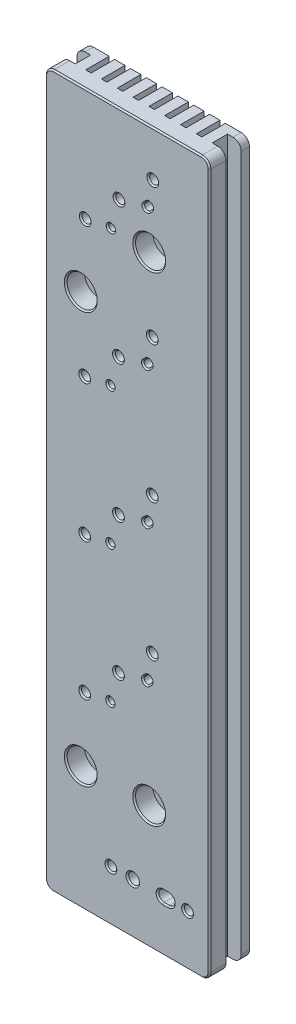
SolidWorks part; units mm, degrees
material "AISI 304"
ref_plane "前视基准面" through (0, 0, 0) normal (0, 0, 1) x (1, 0, 0)
ref_plane "上视基准面" through (0, 0, 0) normal (0, 1, 0) x (1, 0, 0)
ref_plane "右视基准面" through (0, 0, 0) normal (1, 0, 0) x (0, 0, -1)
sketch "草图1" plane through (0, 0, 0) normal (0, 0, 1) x (1, 0, 0)
  line L1 (-1400.8032, -154.6713) -> (-1340.8032, -154.6713)
  line L2 (-1400.8032, -154.6713) -> (-1400.8032, -414.6713)
  line L3 (-1400.8032, -414.6713) -> (-1340.8032, -414.6713)
  line L4 (-1340.8032, -154.6713) -> (-1340.8032, -414.6713)
  line L6 (-1342.8032, -393.0697) -> (-1342.8032, -401.5693) construction
  dimension "D2" = 260
  dimension "D1" = 60
  dimension "D4" = 2
extrude "凸台-拉伸1" add sketch "草图1" along normal up to surface (14.6 mm away)
sketch "草图2" plane through (0, 0, 14.6) normal (0, 0, 1) x (1, 0, 0)
  line L0 (-1362.8011, -194.6713) -> (-1362.8011, -369.6713) construction
  circle A1 centre (-1362.8011, -194.6713) radius 2.5
  dimension "D1" = 175
sketch "草图3" plane through (0, 0, 14.6) normal (0, 0, 1) x (1, 0, 0)
  line L0 (-1362.8011, -194.6713) -> (-1362.8011, -369.6713) construction
  line L1 (-1362.8011, -369.6713) -> (-1387.8011, -369.6713) construction
  line L3 (-1387.8011, -369.6713) -> (-1387.8011, -394.6713) construction
  line L4 (-1387.8011, -369.6713) -> (-1387.8011, -219.6713) construction
  dimension "D1" = 25
  dimension "D2" = 25
  dimension "D3" = 150
  dimension "D5" = 175
sketch "草图6" plane through (0, 0, 14.6) normal (0, 0, 1) x (1, 0, 0)
  line L4 (-1340.8032, -154.6713) -> (-1400.8032, -154.6713)
  line L5 (-1400.8032, -154.6713) -> (-1400.8032, -414.6713)
  line L6 (-1400.8032, -414.6713) -> (-1340.8032, -414.6713)
  line L7 (-1340.8032, -414.6713) -> (-1340.8032, -154.6713)
  line L8 (-1340.8032, -154.6713) -> (-1400.8032, -154.6713)
  line L9 (-1400.8032, -154.6713) -> (-1400.8032, -414.6713)
  line L10 (-1400.8032, -414.6713) -> (-1340.8032, -414.6713)
  line L11 (-1340.8032, -414.6713) -> (-1340.8032, -154.6713)
  circle A21 centre (-1386.1947, -195.9735) radius 2.2225
  circle A22 centre (-1373.8468, -183.6256) radius 2.2225
  circle A23 centre (-1361.4989, -171.2778) radius 2.2225
  circle A26 centre (-1376.8103, -194.1325) radius 1.1938
  circle A27 centre (-1363.3399, -180.6621) radius 1.1938
  circle A33 centre (-1386.1947, -195.9735) radius 2.2225 construction
  circle A34 centre (-1373.8468, -183.6256) radius 2.2225 construction
  circle A35 centre (-1361.4989, -171.2778) radius 2.2225 construction
  circle A36 centre (-1363.3399, -180.6621) radius 1.1938 construction
  circle A37 centre (-1376.8103, -194.1325) radius 1.1938 construction
  dimension "D1" = 0
sketch "草图8" plane through (0, 0, 14.6) normal (0, 0, 1) x (1, 0, 0)
  line L0 (-1363.3399, -180.6621) -> (-1376.8103, -194.1325) construction
  line L1 (-1361.4989, -171.2778) -> (-1373.8468, -183.6256) construction
  line L2 (-1373.8468, -183.6256) -> (-1386.1947, -195.9735) construction
hole_wizard "大小mm 暗销孔5" positions "3D草图6" profile "草图12" hole size "Ø2.5" standard "GB"
sketch3d "3D草图6"
  point P2 (-1376.8103, -194.1325, 14.6)
sketch "草图12" plane through (-1376.8103, -194.1325, 14.6) normal (1, 0, 0) x (0, -1, 0)
  line L0 (0, 0) -> (0, 4.521)
  line L1 (0, 4.521) -> (1.2, 3.8)
  line L2 (1.2, 3.8) -> (1.2, 0)
  line L5 (1.2, 0) -> (0, 0)
  line L10 (0, 4.521) -> (-1.2, 3.8) construction
  line L11 (0, -6.35) -> (0, 107.95) construction
  dimension "孔直径" = 2.4
  dimension "孔深度" = 3.8
  dimension "导头角度" = 118
sketch "草图13" plane through (0, 0, 14.6) normal (0, 0, 1) x (1, 0, 0)
  line L0 (-1362.9156, -180.2379) -> (-1363.7642, -181.0864) construction
  line L3 (-1362.0671, -181.0864) -> (-1362.9156, -181.9349)
  line L4 (-1363.7642, -179.3893) -> (-1364.6127, -180.2379)
  line L5 (-1363.3399, -180.6621) -> (-1376.8103, -194.1325) construction
  arc A2 (-1362.0671, -181.0864) -> (-1363.7642, -179.3893) centre (-1362.9156, -180.2379) ccw
  arc A3 (-1364.6127, -180.2379) -> (-1362.9156, -181.9349) centre (-1363.7642, -181.0864) ccw
  point P2 (-1363.3399, -180.6621)
  dimension "D1" = 1.2
  dimension "D2" = 1.2
extrude "切除-拉伸1" cut sketch "草图13" against normal blind 3.8
hole_wizard "M4 螺纹孔1" positions "3D草图7" profile "草图14" tap size "M4" standard "GB"
sketch3d "3D草图7"
  point P0 (-1386.1947, -195.9735, 14.6)
  point P2 (-1373.8468, -183.6256, 14.6)
  point P4 (-1361.4989, -171.2778, 14.6)
sketch "草图14" plane through (-1386.1947, -195.9735, 14.6) normal (1, 0, 0) x (0, -1, 0)
  line L0 (0, 0) -> (0, 5.9914)
  line L1 (0, 5.9914) -> (1.65, 5)
  line L2 (1.65, 5) -> (1.65, 0)
  line L5 (1.65, 0) -> (0, 0)
  line L10 (0, 5.9914) -> (-1.65, 5) construction
  line L11 (0, -6.35) -> (0, 107.95) construction
  dimension "螺纹孔钻头直径" = 3.3
  dimension "螺纹孔钻头深度" = 5
  dimension "导头角度" = 118
cosmetic thread "孔螺蚊线1" parameters "D1"=5, "D2"=4
cosmetic thread "孔螺蚊线2" parameters "D1"=5, "D2"=4
cosmetic thread "孔螺蚊线3" parameters "D1"=5, "D2"=4
pattern_linear "阵列(线性)1" [suppressed] count 4 spacing 50 of bodies 107
sketch "草图15" plane through (0, 0, 14.6) normal (0, 0, 1) x (1, 0, 0)
  line L0 (-1376.8029, -396.0704) -> (-1348.8032, -396.0697) construction
  line L1 (-1376.8029, -396.0704) -> (-1368.8029, -396.0702) construction
  line L2 (-1348.8032, -396.0697) -> (-1356.8032, -396.0699) construction
  dimension "D1" = 8
  dimension "D2" = 8
hole_wizard "M4 螺纹孔2" positions "3D草图8" profile "草图16" tap size "M4" standard "GB"
sketch3d "3D草图8"
  point P0 (-1376.8029, -396.0704, 14.6)
  point P2 (-1348.8032, -396.0697, 14.6)
sketch "草图16" plane through (-1376.8029, -396.0704, 14.6) normal (1, 0, 0) x (0, -1, 0)
  line L0 (0, 0) -> (0, 5.9914)
  line L1 (0, 5.9914) -> (1.65, 5)
  line L2 (1.65, 5) -> (1.65, 0)
  line L5 (1.65, 0) -> (0, 0)
  line L10 (0, 5.9914) -> (-1.65, 5) construction
  line L11 (0, -6.35) -> (0, 107.95) construction
  dimension "螺纹孔钻头直径" = 3.3
  dimension "螺纹孔钻头深度" = 5
  dimension "导头角度" = 118
cosmetic thread "孔螺蚊线4" parameters "D1"=5, "D2"=4
cosmetic thread "孔螺蚊线5" parameters "D1"=5, "D2"=4
sketch "草图17" plane through (0, 0, 14.6) normal (0, 0, 1) x (1, 0, 0)
  line L0 (-1357.8032, -396.0699) -> (-1355.8032, -396.0699) construction
  line L1 (-1376.8029, -396.0704) -> (-1348.8032, -396.0697) construction
  line L2 (-1357.8032, -394.0699) -> (-1355.8032, -394.0699)
  line L3 (-1357.8031, -398.0699) -> (-1355.8031, -398.0699)
  arc A0 (-1357.8032, -394.0699) -> (-1357.8031, -398.0699) centre (-1357.8032, -396.0699) ccw
  arc A1 (-1355.8031, -398.0699) -> (-1355.8032, -394.0699) centre (-1355.8032, -396.0699) ccw
  point P5 (-1356.8032, -396.0699)
  dimension "D2" = 2
  dimension "D1" = 2
extrude "切除-拉伸2" cut sketch "草图17" against normal blind 5
hole_wizard "大小mm 暗销孔3" positions "3D草图9" profile "草图18" hole size "Ø4.0" standard "GB"
sketch3d "3D草图9"
  point P0 (-1368.8029, -396.0702, 14.6)
sketch "草图18" plane through (-1368.8029, -396.0702, 14.6) normal (1, 0, 0) x (0, -1, 0)
  line L0 (0, 0) -> (0, 6.2017)
  line L1 (0, 6.2017) -> (2, 5)
  line L2 (2, 5) -> (2, 0)
  line L5 (2, 0) -> (0, 0)
  line L10 (0, 6.2017) -> (-2, 5) construction
  line L11 (0, -6.35) -> (0, 107.95) construction
  dimension "孔直径" = 4
  dimension "孔深度" = 5
  dimension "导头角度" = 118
sketch "草图19" plane through (0, 0, 0) normal (0, 0, -1) x (-1, 0, 0)
  line L0 (1340.8032, -154.6713) -> (1400.8032, -154.6713) construction
  line L1 (1343.8032, -154.6713) -> (1345.8032, -154.6713)
  line L2 (1343.8032, -154.6713) -> (1343.8032, -414.6713)
  line L3 (1343.8032, -414.6713) -> (1345.8032, -414.6713)
  line L4 (1345.8032, -154.6713) -> (1345.8032, -414.6713)
  line L5 (1400.8032, -414.6713) -> (1340.8032, -414.6713) construction
  line L6 (1340.8032, -414.6713) -> (1340.8032, -154.6713) construction
  dimension "D1" = 2
  dimension "D2" = 3
extrude "切除-拉伸3" cut sketch "草图19" against normal offset from surface (8.6 mm away) 6 up to face at (-1368.8029, -398.0702, 14.6)
pattern_linear "阵列(线性)2" count 10 spacing 5.7778 along (-1, 0, 0) of "切除-拉伸3"
sketch "草图20" plane through (0, 0, 0) normal (0, 0, -1) x (-1, 0, 0)
  line L0 (1384.2476, -154.6713) -> (1384.2476, -414.6713) construction
  line L1 (1384.2476, -213.6713) -> (1392.0254, -213.6713)
  line L2 (1384.2476, -213.6713) -> (1384.2476, -236.6713)
  line L3 (1384.2476, -236.6713) -> (1392.0254, -236.6713)
  line L4 (1392.0254, -213.6713) -> (1392.0254, -236.6713)
  line L5 (1392.0254, -414.6713) -> (1392.0254, -154.6713) construction
  line L6 (1392.0254, -414.6713) -> (1392.0254, -154.6713) construction
  line L7 (1384.2476, -352.6713) -> (1392.0254, -352.6713)
  line L8 (1384.2476, -352.6713) -> (1384.2476, -375.6713)
  line L9 (1384.2476, -375.6713) -> (1392.0254, -375.6713)
  line L10 (1392.0254, -352.6713) -> (1392.0254, -375.6713)
  line L12 (1355.3587, -188.6713) -> (1368.9143, -188.6713)
  line L13 (1355.3587, -188.6713) -> (1355.3587, -211.6713)
  line L14 (1355.3587, -211.6713) -> (1368.9143, -211.6713)
  line L15 (1368.9143, -188.6713) -> (1368.9143, -211.6713)
  line L16 (1368.9143, -395.7535) -> (1368.9143, -154.6713) construction
  line L18 (1355.3587, -352.6713) -> (1368.9143, -352.6713)
  line L19 (1355.3587, -352.6713) -> (1355.3587, -375.6713)
  line L20 (1355.3587, -375.6713) -> (1368.9143, -375.6713)
  line L21 (1368.9143, -352.6713) -> (1368.9143, -375.6713)
  line L22 (1355.3587, -194.6713) -> (1368.9143, -194.6713) construction
  line L23 (1384.2476, -219.6713) -> (1392.0254, -219.6713) construction
  line L24 (1355.3587, -369.6713) -> (1368.9143, -369.6713) construction
  line L25 (1384.2476, -369.6713) -> (1392.0254, -369.6713) construction
  line L26 (1355.3587, -154.6713) -> (1355.3587, -414.6713) construction
  line L27 (1362.1365, -369.6713) -> (1362.1365, -375.6713) construction
  line L28 (1362.1365, -188.6713) -> (1362.1365, -194.6713) construction
  line L29 (1388.1365, -213.6713) -> (1388.1365, -219.6713) construction
  line L30 (1388.1365, -369.6713) -> (1388.1365, -375.6713) construction
  dimension "D1" = 23
  dimension "D2" = 6
extrude "凸台-拉伸2" add sketch "草图20" against normal up to surface (8.6 mm away) up to face at (-1362.1365, -284.6713, 8.6)
hole_wizard "打孔尺寸(%根据)内六角圆柱头螺钉的类型2" positions "3D草图2" profile "草图5" counterbore size "M6" standard "GB" end condition through all
sketch3d "3D草图2"
  point P0 (-1387.8011, -369.6713, 14.6)
  point P3 (-1387.8011, -219.6713, 14.6)
sketch "草图5" plane through (-1387.8011, -369.6713, 14.6) normal (1, 0, 0) x (0, -1, 0)
  line L0 (0, 0) -> (0, 14.6)
  line L1 (0, 14.6) -> (3.3, 14.6)
  line L3 (3.3, 14.6) -> (3.3, 6.8)
  line L4 (3.3, 6.8) -> (5.5, 6.8)
  line L5 (5.5, 6.8) -> (5.5, 0)
  line L7 (5.5, 0) -> (0, 0)
  line L11 (0, -6.35) -> (0, 107.95) construction
  dimension "通孔孔直径" = 6.6
  dimension "通孔孔深度" = 14.6
  dimension "柱形沉头孔直径" = 11
  dimension "柱形沉头孔深度" = 6.8
hole_wizard "打孔尺寸(%根据)内六角圆柱头螺钉的类型1" positions "3D草图1" profile "草图4" counterbore size "M6" standard "GB" end condition through all
sketch3d "3D草图1"
  point P0 (-1362.8011, -194.6713, 14.6)
  point P3 (-1362.8011, -369.6713, 14.6)
sketch "草图4" plane through (-1362.8011, -194.6713, 14.6) normal (1, 0, 0) x (0, -1, 0)
  line L0 (0, 0) -> (0, 14.6)
  line L1 (0, 14.6) -> (3.3, 14.6)
  line L3 (3.3, 14.6) -> (3.3, 6.8)
  line L4 (3.3, 6.8) -> (5.5, 6.8)
  line L5 (5.5, 6.8) -> (5.5, 0)
  line L7 (5.5, 0) -> (0, 0)
  line L11 (0, -6.35) -> (0, 107.95) construction
  dimension "通孔孔直径" = 6.6
  dimension "通孔孔深度" = 14.6
  dimension "柱形沉头孔直径" = 11
  dimension "柱形沉头孔深度" = 6.8
sketch "草图21" plane through (0, 0, 0) normal (0, 0, -1) x (-1, 0, 0)
  line L0 (1362.8011, -194.6713) -> (1362.8011, -204.6713) construction
  line L1 (1362.8011, -194.6713) -> (1362.8011, -369.6713) construction
  line L2 (1387.8011, -219.6713) -> (1387.8011, -229.6713) construction
  line L3 (1387.8011, -369.6713) -> (1387.8011, -219.6713) construction
  line L4 (1362.8011, -369.6713) -> (1362.8011, -359.6713) construction
  line L5 (1387.8011, -369.6713) -> (1387.8011, -359.6713) construction
  dimension "D1" = 10
hole_wizard "大小mm 暗销孔4" positions "3D草图10" profile "草图22" hole size "Ø4.0" standard "GB"
sketch3d "3D草图10"
  point P0 (-1362.8011, -359.6713, 0)
  point P3 (-1387.8011, -359.6713, 0)
sketch "草图22" plane through (-1362.8011, -359.6713, 0) normal (1, 0, 0) x (0, 1, 0)
  line L0 (0, 0) -> (0, 6.2017)
  line L1 (0, 6.2017) -> (2, 5)
  line L2 (2, 5) -> (2, 0)
  line L5 (2, 0) -> (0, 0)
  line L10 (0, 6.2017) -> (-2, 5) construction
  line L11 (0, -6.35) -> (0, 107.95) construction
  dimension "孔直径" = 4
  dimension "孔深度" = 5
  dimension "导头角度" = 118
sketch "草图23" plane through (0, 0, 0) normal (0, 0, -1) x (-1, 0, 0)
  line L0 (1362.8011, -203.6713) -> (1362.8011, -205.6713) construction
  line L1 (1362.8011, -194.6713) -> (1362.8011, -369.6713) construction
  line L2 (1364.8011, -203.6713) -> (1364.8011, -205.6713)
  line L3 (1360.8011, -203.6713) -> (1360.8011, -205.6713)
  line L4 (1387.8011, -228.6713) -> (1387.8011, -230.6713) construction
  line L5 (1387.8011, -369.6713) -> (1387.8011, -219.6713) construction
  line L6 (1389.8011, -228.6713) -> (1389.8011, -230.6713)
  line L7 (1385.8011, -228.6713) -> (1385.8011, -230.6713)
  arc A0 (1364.8011, -203.6713) -> (1360.8011, -203.6713) centre (1362.8011, -203.6713) ccw
  arc A1 (1360.8011, -205.6713) -> (1364.8011, -205.6713) centre (1362.8011, -205.6713) ccw
  arc A2 (1389.8011, -228.6713) -> (1385.8011, -228.6713) centre (1387.8011, -228.6713) ccw
  arc A3 (1385.8011, -230.6713) -> (1389.8011, -230.6713) centre (1387.8011, -230.6713) ccw
  point P5 (1362.8011, -204.6713)
  point P11 (1387.8011, -229.6713)
  dimension "D2" = 2
  dimension "D1" = 2
extrude "切除-拉伸4" cut sketch "草图23" against normal blind 5
fillet "圆角1" radius 3 4 edges at (-1340.8032, -154.6713, 7.3) (-1340.8032, -414.6713, 7.3) (-1400.8032, -154.6713, 7.3) (-1400.8032, -414.6713, 7.3)
chamfer "倒角1" [suppressed] distance 0.5 angle 45
sketch "草图24" plane through (0, 0, 14.6) normal (0, 0, 1) x (1, 0, 0)
  line L4 (-1340.8032, -411.6713) -> (-1340.8032, -157.6713)
  line L5 (-1340.8032, -411.6713) -> (-1340.8032, -157.6713)
  line L6 (-1343.8032, -154.6713) -> (-1397.8032, -154.6713)
  line L7 (-1343.8032, -154.6713) -> (-1397.8032, -154.6713)
  line L12 (-1400.8032, -157.6713) -> (-1400.8032, -411.6713)
  line L13 (-1400.8032, -157.6713) -> (-1400.8032, -411.6713)
  line L14 (-1397.8032, -414.6713) -> (-1343.8032, -414.6713)
  line L15 (-1397.8032, -414.6713) -> (-1343.8032, -414.6713)
  circle A0 centre (-1386.3743, -245.7939) radius 2.2225 construction
  circle A1 centre (-1374.0264, -233.446) radius 2.2225 construction
  circle A2 centre (-1361.6786, -221.0981) radius 2.2225 construction
  circle A3 centre (-1386.3743, -245.7939) radius 2.2225
  circle A4 centre (-1374.0264, -233.446) radius 2.2225
  circle A5 centre (-1361.6786, -221.0981) radius 2.2225
  circle A6 centre (-1363.5195, -330.4825) radius 1.1938 construction
  circle A7 centre (-1376.9899, -343.9529) radius 1.1938 construction
  circle A8 centre (-1386.3743, -345.7939) radius 2.2225 construction
  circle A9 centre (-1374.0264, -333.446) radius 2.2225 construction
  arc A10 (-1340.8032, -157.6713) -> (-1343.8032, -154.6713) centre (-1343.8032, -157.6713) ccw
  arc A11 (-1340.8032, -157.6713) -> (-1343.8032, -154.6713) centre (-1343.8032, -157.6713) ccw
  arc A12 (-1397.8032, -154.6713) -> (-1400.8032, -157.6713) centre (-1397.8032, -157.6713) ccw
  arc A13 (-1397.8032, -154.6713) -> (-1400.8032, -157.6713) centre (-1397.8032, -157.6713) ccw
  circle A18 centre (-1361.6786, -321.0981) radius 2.2225 construction
  circle A19 centre (-1363.5195, -280.4825) radius 1.1938 construction
  circle A20 centre (-1376.9899, -293.9529) radius 1.1938 construction
  circle A21 centre (-1386.3743, -295.7939) radius 2.2225 construction
  circle A22 centre (-1374.0264, -283.446) radius 2.2225 construction
  circle A23 centre (-1361.6786, -271.0981) radius 2.2225 construction
  circle A24 centre (-1363.5195, -230.4825) radius 1.1938 construction
  circle A25 centre (-1376.9899, -243.9529) radius 1.1938 construction
  circle A26 centre (-1363.5195, -330.4825) radius 1.1938
  circle A27 centre (-1376.9899, -343.9529) radius 1.1938
  circle A28 centre (-1386.3743, -345.7939) radius 2.2225
  circle A29 centre (-1374.0264, -333.446) radius 2.2225
  circle A30 centre (-1361.6786, -321.0981) radius 2.2225
  circle A31 centre (-1363.5195, -280.4825) radius 1.1938
  circle A32 centre (-1376.9899, -293.9529) radius 1.1938
  circle A33 centre (-1386.3743, -295.7939) radius 2.2225
  circle A34 centre (-1374.0264, -283.446) radius 2.2225
  circle A35 centre (-1361.6786, -271.0981) radius 2.2225
  circle A36 centre (-1363.5195, -230.4825) radius 1.1938
  circle A37 centre (-1376.9899, -243.9529) radius 1.1938
  arc A42 (-1400.8032, -411.6713) -> (-1397.8032, -414.6713) centre (-1397.8032, -411.6713) ccw
  arc A43 (-1400.8032, -411.6713) -> (-1397.8032, -414.6713) centre (-1397.8032, -411.6713) ccw
  arc A44 (-1343.8032, -414.6713) -> (-1340.8032, -411.6713) centre (-1343.8032, -411.6713) ccw
  arc A45 (-1343.8032, -414.6713) -> (-1340.8032, -411.6713) centre (-1343.8032, -411.6713) ccw
  dimension "D1" = 0
sketch "草图29" plane through (0, 0, 14.6) normal (0, 0, 1) x (1, 0, 0)
  line L0 (-1386.3743, -345.7939) -> (-1374.0264, -333.446) construction
  line L1 (-1374.0264, -333.446) -> (-1361.6786, -321.0981) construction
hole_wizard "M4 螺纹孔4" positions "3D草图18" profile "草图33" tap size "M4" standard "GB"
sketch3d "3D草图18"
  point P0 (-1361.6786, -321.0981, 14.6)
  point P2 (-1374.0264, -333.446, 14.6)
  point P4 (-1386.3743, -345.7939, 14.6)
  point P6 (-1386.3743, -295.7939, 14.6)
  point P8 (-1374.0264, -283.446, 14.6)
  point P10 (-1361.6786, -271.0981, 14.6)
  point P12 (-1361.6786, -221.0981, 14.6)
  point P14 (-1374.0264, -233.446, 14.6)
  point P16 (-1386.3743, -245.7939, 14.6)
sketch "草图33" plane through (-1361.6786, -321.0981, 14.6) normal (1, 0, 0) x (0, -1, 0)
  line L0 (0, 0) -> (0, 5.9914)
  line L1 (0, 5.9914) -> (1.65, 5)
  line L2 (1.65, 5) -> (1.65, 0)
  line L5 (1.65, 0) -> (0, 0)
  line L10 (0, 5.9914) -> (-1.65, 5) construction
  line L11 (0, -6.35) -> (0, 107.95) construction
  dimension "螺纹孔钻头直径" = 3.3
  dimension "螺纹孔钻头深度" = 5
  dimension "导头角度" = 118
cosmetic thread "孔螺蚊线9" parameters "D1"=5, "D2"=4
cosmetic thread "孔螺蚊线10" parameters "D1"=5, "D2"=4
cosmetic thread "孔螺蚊线11" parameters "D1"=5, "D2"=4
cosmetic thread "孔螺蚊线12" parameters "D1"=5, "D2"=4
cosmetic thread "孔螺蚊线13" parameters "D1"=5, "D2"=4
cosmetic thread "孔螺蚊线14" parameters "D1"=5, "D2"=4
cosmetic thread "孔螺蚊线15" parameters "D1"=5, "D2"=4
cosmetic thread "孔螺蚊线16" parameters "D1"=5, "D2"=4
cosmetic thread "孔螺蚊线17" parameters "D1"=5, "D2"=4
hole_wizard "大小mm 暗销孔5" positions "3D草图19" profile "草图34" hole size "Ø2.5" standard "GB"
sketch3d "3D草图19"
  point P0 (-1376.9899, -243.9529, 14.6)
  point P2 (-1376.9899, -293.9529, 14.6)
  point P4 (-1376.9899, -343.9529, 14.6)
sketch "草图34" plane through (-1376.9899, -243.9529, 14.6) normal (1, 0, 0) x (0, -1, 0)
  line L0 (0, 0) -> (0, 4.521)
  line L1 (0, 4.521) -> (1.2, 3.8)
  line L2 (1.2, 3.8) -> (1.2, 0)
  line L5 (1.2, 0) -> (0, 0)
  line L10 (0, 4.521) -> (-1.2, 3.8) construction
  line L11 (0, -6.35) -> (0, 107.95) construction
  dimension "孔直径" = 2.4
  dimension "孔深度" = 3.8
  dimension "导头角度" = 118
sketch "草图35" plane through (0, 0, 14.6) normal (0, 0, 1) x (1, 0, 0)
  line L0 (-1363.0952, -230.0582) -> (-1363.9438, -230.9068) construction
  line L1 (-1362.2467, -230.9068) -> (-1363.0952, -231.7553)
  line L2 (-1363.9438, -229.2097) -> (-1364.7923, -230.0582)
  line L3 (-1363.0952, -280.0582) -> (-1363.9438, -280.9068) construction
  line L4 (-1362.2467, -280.9068) -> (-1363.0952, -281.7553)
  line L5 (-1363.9438, -279.2097) -> (-1364.7923, -280.0582)
  line L6 (-1363.0952, -330.0582) -> (-1363.9438, -330.9068) construction
  line L7 (-1362.2467, -330.9068) -> (-1363.0952, -331.7553)
  line L8 (-1363.9438, -329.2097) -> (-1364.7923, -330.0582)
  arc A0 (-1362.2467, -230.9068) -> (-1363.9438, -229.2097) centre (-1363.0952, -230.0582) ccw
  arc A1 (-1364.7923, -230.0582) -> (-1363.0952, -231.7553) centre (-1363.9438, -230.9068) ccw
  arc A2 (-1362.2467, -280.9068) -> (-1363.9438, -279.2097) centre (-1363.0952, -280.0582) ccw
  arc A3 (-1364.7923, -280.0582) -> (-1363.0952, -281.7553) centre (-1363.9438, -280.9068) ccw
  arc A4 (-1362.2467, -330.9068) -> (-1363.9438, -329.2097) centre (-1363.0952, -330.0582) ccw
  arc A5 (-1364.7923, -330.0582) -> (-1363.0952, -331.7553) centre (-1363.9438, -330.9068) ccw
  point P2 (-1363.5195, -230.4825)
  point P9 (-1363.5195, -280.4825)
  point P18 (-1363.5195, -330.4825)
  dimension "D2" = 1.2
  dimension "D1" = 1.2
extrude "切除-拉伸5" cut sketch "草图35" against normal blind 3.8
chamfer "倒角2" distance 0.5 angle 45 51 edges at (-1341.6819, -413.7926, 14.6) (-1370.8032, -414.6713, 14.6) (-1399.9245, -413.7926, 14.6) (-1400.8032, -284.6713, 14.6) (-1399.9245, -155.55, 14.6) (-1370.8032, -154.6713, 14.6) (-1341.6819, -155.55, 14.6) (-1340.8032, -284.6713, 14.6) (-1376.8103, -195.3325, 14.6) (-1364.1884, -179.8136, 14.6) (-1364.6127, -181.9349, 14.6) (-1362.4914, -181.5106, 14.6) (-1362.0671, -179.3893, 14.6) (-1361.4989, -172.9278, 14.6) (-1373.8468, -185.2756, 14.6) (-1386.1947, -197.6235, 14.6) (-1348.8032, -397.7197, 14.6) (-1376.8029, -397.7204, 14.6) (-1356.8031, -398.0699, 14.6) (-1353.8032, -396.0698, 14.6) (-1356.8032, -394.0699, 14.6) (-1359.8032, -396.07, 14.6) (-1368.8029, -398.0702, 14.6) (-1387.8011, -225.1713, 14.6) (-1387.8011, -375.1713, 14.6) (-1362.8011, -375.1713, 14.6) (-1362.8011, -200.1713, 14.6) (-1386.3743, -247.4439, 14.6) (-1374.0264, -235.096, 14.6) (-1361.6786, -222.7481, 14.6) (-1361.6786, -272.7481, 14.6) (-1374.0264, -285.096, 14.6) (-1386.3743, -297.4439, 14.6) (-1386.3743, -347.4439, 14.6) (-1374.0264, -335.096, 14.6) (-1361.6786, -322.7481, 14.6) (-1376.9899, -345.1529, 14.6) (-1376.9899, -295.1529, 14.6) (-1376.9899, -245.1529, 14.6) (-1364.368, -329.634, 14.6) (-1364.7923, -331.7553, 14.6) (-1362.671, -331.331, 14.6) (-1362.2467, -329.2097, 14.6) (-1364.368, -279.634, 14.6) (-1364.7923, -281.7553, 14.6) (-1362.671, -281.331, 14.6) (-1362.2467, -279.2097, 14.6) (-1364.368, -229.634, 14.6) (-1364.7923, -231.7553, 14.6) (-1362.671, -231.331, 14.6) (-1362.2467, -229.2097, 14.6)
sketch "草图36" plane through (0, -414.6713, 0) normal (0, -1, 0) x (1, 0, 0)
  line L1 (-1395.8032, 8.6) -> (-1400.8032, 8.6)
  line L2 (-1395.8032, 8.6) -> (-1395.8032, 0)
  line L3 (-1395.8032, 0) -> (-1400.8032, 0)
  line L4 (-1400.8032, 8.6) -> (-1400.8032, 0)
  line L5 (-1345.8032, 8.6) -> (-1340.8032, 8.6)
  line L6 (-1345.8032, 8.6) -> (-1345.8032, 0)
  line L7 (-1345.8032, 0) -> (-1340.8032, 0)
  line L8 (-1340.8032, 8.6) -> (-1340.8032, 0)
extrude "切除-拉伸6" cut sketch "草图36" against normal through all
sketch "草图37" plane through (0, -414.6713, 0) normal (0, -1, 0) x (1, 0, 0)
  line L0 (-1340.8032, 14.1) -> (-1340.8032, 8.6) construction
  line L1 (-1395.8032, 0) -> (-1400.8032, 0)
  line L2 (-1395.8032, 0) -> (-1395.8032, 3)
  line L3 (-1395.8032, 3) -> (-1400.8032, 3)
  line L4 (-1400.8032, 0) -> (-1400.8032, 3)
  line L5 (-1345.8032, 0) -> (-1340.8032, 0)
  line L6 (-1345.8032, 0) -> (-1345.8032, 3)
  line L7 (-1345.8032, 3) -> (-1340.8032, 3)
  line L8 (-1340.8032, 0) -> (-1340.8032, 3)
  line L9 (-1400.8032, 8.6) -> (-1400.8032, 14.1) construction
  dimension "D1" = 3
extrude "凸台-拉伸3" add sketch "草图37" against normal through all
fillet "圆角2" radius 3 4 edges at (-1340.8032, -154.6713, 1.5) (-1400.8032, -154.6713, 1.5) (-1340.8032, -414.6713, 1.5) (-1400.8032, -414.6713, 1.5)
